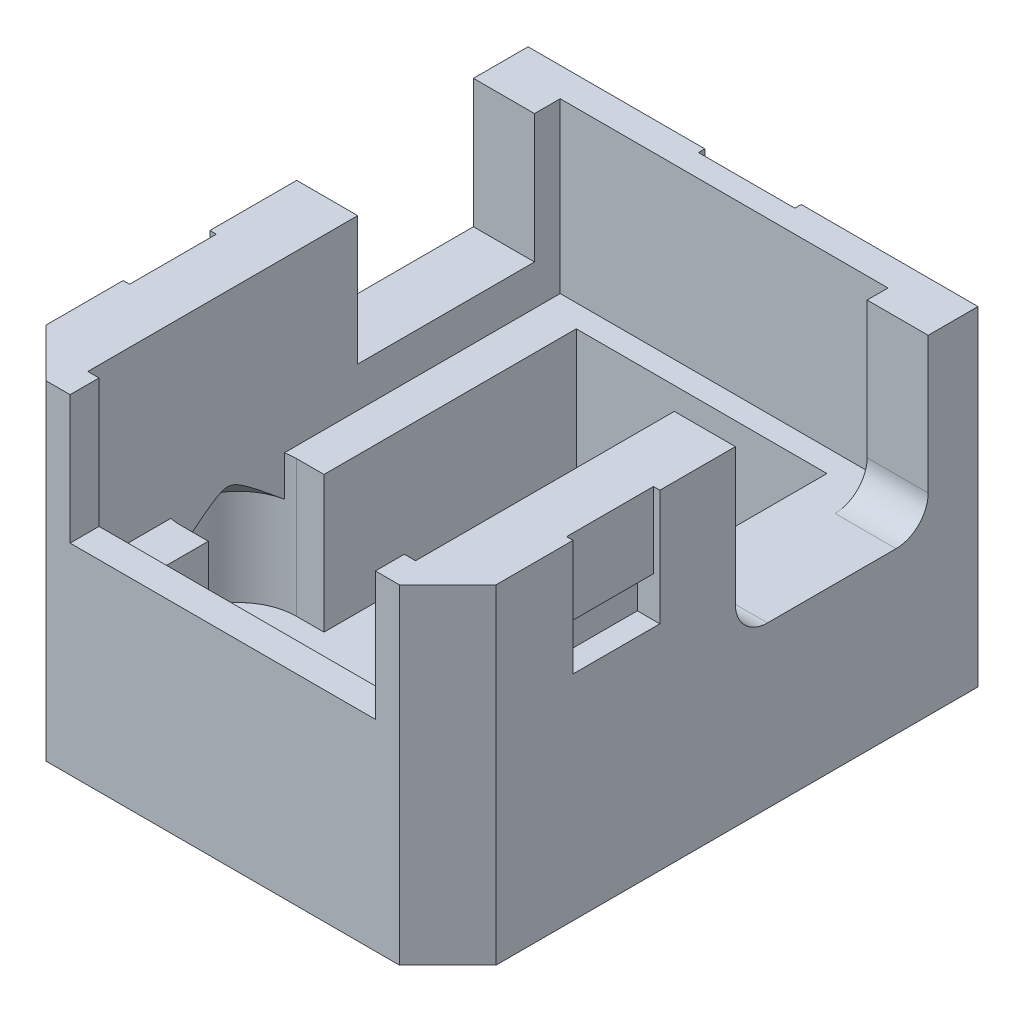
SolidWorks part; units mm, degrees
ref_plane "Płaszczyzna przednia" through (0, 0, 0) normal (0, 0, 1) x (1, 0, 0)
ref_plane "Płaszczyzna górna" through (0, 0, 0) normal (0, 1, 0) x (1, 0, 0)
ref_plane "Płaszczyzna prawa" through (0, 0, 0) normal (1, 0, 0) x (0, 0, -1)
sketch "Szkic1" plane through (0, 0, 0) normal (0, 1, 0) x (1, 0, 0)
  line L1 (-14, -16.5) -> (14, -16.5)
  line L2 (-14, -16.5) -> (-14, 16.5)
  line L3 (-14, 16.5) -> (14, 16.5)
  line L4 (14, -16.5) -> (14, 16.5)
  line L5 (-14, -16.5) -> (14, 16.5) construction
  line L6 (-14, 16.5) -> (14, -16.5) construction
  point P0 (0, 0)
  dimension "D1" = 28
  dimension "D2" = 33
extrude "Dodanie-wyciągnięcie1" add sketch "Szkic1" along normal blind 1.5
sketch "Szkic2" plane through (0, 1.5, 0) normal (0, 1, 0) x (1, 0, 0)
  line L0 (-14, 16.5) -> (14, 16.5)
  line L1 (14, 16.5) -> (14, -16.5)
  line L2 (14, -16.5) -> (-14, -16.5)
  line L3 (-14, -16.5) -> (-14, 16.5)
  line L5 (-10.2, -14.7) -> (10.2, -14.7)
  line L6 (-10.2, -14.7) -> (-10.2, 14.7)
  line L7 (-10.2, 14.7) -> (10.2, 14.7)
  line L8 (10.2, -14.7) -> (10.2, 14.7)
  line L9 (-10.2, -14.7) -> (10.2, 14.7) construction
  line L10 (-10.2, 14.7) -> (10.2, -14.7) construction
  point P4 (0, 0)
  dimension "D1" = 1.8
  dimension "D2" = 3.8
  dimension "D3" = 3.8
  dimension "D4" = 1.8
extrude "Dodanie-wyciągnięcie2" add sketch "Szkic2" along normal blind 19
sketch "Szkic7" plane through (0, 1.5, 0) normal (0, 1, 0) x (1, 0, 0)
  line L1 (-10.2, -14.7) -> (10.2, -14.7)
  line L2 (-10.2, -14.7) -> (-10.2, 14.7)
  line L3 (-10.2, 14.7) -> (10.2, 14.7)
  line L4 (10.2, -14.7) -> (10.2, 14.7)
  line L5 (-10.2, -14.7) -> (10.2, 14.7) construction
  line L6 (-10.2, 14.7) -> (10.2, -14.7) construction
  line L7 (-7.8, -13.3) -> (7.8, -13.3)
  line L8 (-7.8, -13.3) -> (-7.8, 13.3)
  line L9 (-7.8, 13.3) -> (7.8, 13.3)
  line L10 (7.8, -13.3) -> (7.8, 13.3)
  line L11 (-7.8, -13.3) -> (7.8, 13.3) construction
  line L12 (-7.8, 13.3) -> (7.8, -13.3) construction
  point P0 (0, 0)
  point P7 (0, 0)
  dimension "D1" = 1.4
  dimension "D2" = 2.4
extrude "Dodanie-wyciągnięcie4" add sketch "Szkic7" along normal blind 8.5
sketch "Szkic3" plane through (14, 0, 0) normal (1, 0, 0) x (0, 0, -1)
  line L0 (16.5, 0) -> (16.5, 10) construction
  line L1 (16.5, 20.5) -> (16.5, 0) construction
  line L2 (16.5, 10) -> (13.4, 10) construction
  line L3 (13.4, 10) -> (1.4, 10)
  line L4 (1.4, 10) -> (1.4, 20.5)
  line L5 (-16.5, 20.5) -> (16.5, 20.5) construction
  line L6 (1.4, 20.5) -> (13.4, 20.5)
  line L7 (13.4, 20.5) -> (13.4, 10)
  dimension "D1" = 3.1
  dimension "D2" = 12
  dimension "D4" = 10.5
extrude "Wytnij-wyciągnięcie1" cut sketch "Szkic3" against normal up to surface (3.8 mm away) contours L3 L4 L6 L7 up to face at (10.2, 15.25, 0)
sketch "Szkic4" plane through (0, 0, 16.5) normal (0, 0, 1) x (1, 0, 0)
  line L0 (14, 0) -> (14, 12.5) construction
  line L1 (-14, 0) -> (14, 0) construction
  line L2 (14, 20.5) -> (14, 0) construction
  line L3 (14, 12.5) -> (9.5, 12.5) construction
  line L4 (9.5, 12.5) -> (9.5, 20.5)
  line L5 (-14, 20.5) -> (14, 20.5) construction
  line L6 (9.5, 20.5) -> (-9.5, 20.5)
  line L7 (-9.5, 20.5) -> (-9.5, 12.5)
  line L8 (-9.5, 12.5) -> (9.5, 12.5)
  line L9 (-14, 20.5) -> (-14, 0) construction
  dimension "D1" = 4.5
  dimension "D2" = 4.5
  dimension "D4" = 8
extrude "Wytnij-wyciągnięcie2" cut sketch "Szkic4" against normal up to surface (1.8 mm away) up to face at (0, 15.25, 14.7)
sketch "Szkic5" plane through (-14, 0, 0) normal (-1, 0, 0) x (0, 0, 1)
  line L0 (-16.5, 0) -> (-16.5, 12.5) construction
  line L1 (-16.5, 0) -> (16.5, 0) construction
  line L2 (-16.5, 20.5) -> (-16.5, 0) construction
  line L3 (-16.5, 12.5) -> (-13.1, 12.5) construction
  line L4 (-13.1, 12.5) -> (-13.1, 20.5)
  line L5 (-13.1, 20.5) -> (-2.1, 20.5)
  line L6 (-2.1, 20.5) -> (-2.1, 12.5)
  line L7 (-2.1, 12.5) -> (-13.1, 12.5)
  line L8 (-16.5, 20.5) -> (16.5, 20.5) construction
  dimension "D1" = 3.4
  dimension "D3" = 11
  dimension "D4" = 8
extrude "Wytnij-wyciągnięcie3" cut sketch "Szkic5" against normal up to surface (3.8 mm away) up to face at (-10.2, 15.25, 0)
sketch "Szkic8" plane through (0, 0, 0) normal (0, -1, 0) x (1, 0, 0)
  line L0 (0, 0) -> (0, 6) construction
  line L1 (-9.5, 6) -> (9.5, 6) construction
  line L2 (9.5, 6) -> (4.5, 6) construction
  line L3 (9.5, 4.35) -> (4.5, 4.35)
  line L4 (9.5, 7.65) -> (4.5, 7.65)
  line L5 (-9.5, 6) -> (-4.5, 6) construction
  line L6 (-9.5, 4.35) -> (-4.5, 4.35)
  line L7 (-9.5, 7.65) -> (-4.5, 7.65)
  arc A1 (9.5, 4.35) -> (9.5, 7.65) centre (9.5, 6) ccw
  arc A2 (4.5, 7.65) -> (4.5, 4.35) centre (4.5, 6) ccw
  arc A3 (-9.5, 4.35) -> (-9.5, 7.65) centre (-9.5, 6) cw
  arc A4 (-4.5, 7.65) -> (-4.5, 4.35) centre (-4.5, 6) cw
  point P3 (7, 6)
  point P6 (0, 6)
  point P13 (-7, 6)
  dimension "D3" = 5
  dimension "D4" = 1.65
  dimension "D1" = 6
  dimension "D2" = 19
extrude "Wytnij-wyciągnięcie4" cut sketch "Szkic8" against normal up to surface (10 mm away) up to face at (6.05, 10, -3.7)
sketch "Szkic9" plane through (0, 0, 0) normal (0, -1, 0) x (1, 0, 0)
  line L0 (0, 0) -> (0, -4.7269) construction
  line L1 (-9.5, 2.4) -> (-5.0017, 2.4)
  line L2 (-5.0017, 2.4) -> (-5.0017, 9.6)
  line L3 (-5.0017, 9.6) -> (-9.5, 9.6)
  line L5 (0, -0.825) -> (0, 0.825) construction
  line L6 (5.0017, 9.6) -> (9.5, 9.6)
  line L7 (5.0017, 2.4) -> (5.0017, 9.6)
  line L8 (9.5, 2.4) -> (5.0017, 2.4)
  arc A0 (-9.5, 9.6) -> (-9.5, 2.4) centre (-9.5, 6) ccw
  arc A2 (-9.5, 2.4) -> (-9.5, 9.6) centre (-9.5, 6) ccw construction
  arc A3 (9.5, 2.4) -> (9.5, 9.6) centre (9.5, 6) cw construction
  arc A4 (9.5, 9.6) -> (9.5, 2.4) centre (9.5, 6) cw
  dimension "D1" = 7.2
extrude "Wytnij-wyciągnięcie8" cut sketch "Szkic9" against normal up to surface (10 mm away) from surface up to face at (3.4571, 10, -4.2332) starting at face at (0, 1.5, 4)
fillet "Zaokrąglenie1" radius 2 2 edges at (12.1, 10, -1.4) (12.1, 10, -13.4)
sketch "Szkic10" plane through (14, 0, 0) normal (1, 0, 0) x (0, 0, -1)
  line L0 (-16.5, 20.5) -> (-8.7, 20.5) construction
  line L1 (-16.5, 20.5) -> (1.4, 20.5) construction
  line L2 (-8.7, 20.5) -> (-8.7, 13.3)
  line L3 (-8.7, 13.3) -> (-3.3, 13.3)
  line L4 (-3.3, 13.3) -> (-3.3, 20.5)
  line L5 (-3.3, 20.5) -> (-8.7, 20.5)
  dimension "D1" = 7.2
  dimension "D2" = 7.8
  dimension "D3" = 5.4
extrude "Wytnij-wyciągnięcie9" cut sketch "Szkic10" against normal blind 0.4
sketch "Szkic11" plane through (13.6, 0, 0) normal (1, 0, 0) x (0, 0, -1)
  line L0 (-3.3, 13.3) -> (-3.3, 20.5) construction
  line L1 (-8.7, 13.3) -> (-3.3, 13.3)
  line L2 (-8.7, 13.3) -> (-8.7, 15.8)
  line L3 (-8.7, 15.8) -> (-3.3, 15.8)
  line L4 (-3.3, 13.3) -> (-3.3, 15.8)
  line L5 (-8.7, 13.3) -> (-3.3, 15.8) construction
  line L6 (-8.7, 15.8) -> (-3.3, 13.3) construction
  point P4 (-6, 14.55)
  dimension "D1" = 2.5
extrude "Wytnij-wyciągnięcie10" cut sketch "Szkic11" against normal blind 1
sketch "Szkic12" plane through (0, 0, -16.5) normal (0, 0, -1) x (-1, 0, 0)
  line L0 (-3, 20.5) -> (3, 20.5)
  line L2 (-14, 20.5) -> (14, 20.5) construction
  line L3 (3, 20.5) -> (3, 13.3)
  line L4 (3, 13.3) -> (-3, 13.3)
  line L5 (-3, 13.3) -> (-3, 20.5)
  point P5 (0, 20.5)
  dimension "D1" = 6
  dimension "D2" = 7.2
extrude "Wytnij-wyciągnięcie11" cut sketch "Szkic12" against normal blind 0.4
sketch "Szkic13" plane through (0, 0, -16.1) normal (0, 0, -1) x (-1, 0, 0)
  line L0 (3, 13.3) -> (3, 20.5) construction
  line L1 (-3, 13.3) -> (3, 13.3)
  line L2 (-3, 13.3) -> (-3, 15.8)
  line L3 (-3, 15.8) -> (3, 15.8)
  line L4 (3, 13.3) -> (3, 15.8)
  line L5 (-3, 13.3) -> (3, 15.8) construction
  line L6 (-3, 15.8) -> (3, 13.3) construction
  point P4 (0, 14.55)
  dimension "D1" = 2.5
extrude "Wytnij-wyciągnięcie12" cut sketch "Szkic13" against normal blind 1
mirror "Lustro1" about plane through (0, 0, 0) normal (1, 0, 0) of "Wytnij-wyciągnięcie10", "Wytnij-wyciągnięcie9"
chamfer "Sfazowanie1" distance 1 angle 45 3 edges at (12.6, 15.8, 6) (0, 15.8, -15.1) (-12.6, 15.8, 6)
chamfer "Sfazowanie2" distance 3 angle 45 2 edges at (14, 10.25, 16.5) (-14, 10.25, 16.5)
chamfer "Sfazowanie3" distance 2.5 angle 50 2 edges at (13.1, 10, 6) (-13.1, 10, 6) first distance on face at (10.8172, 7.1667, 6) first distance on face at (-10.8172, 7.1667, 6)
